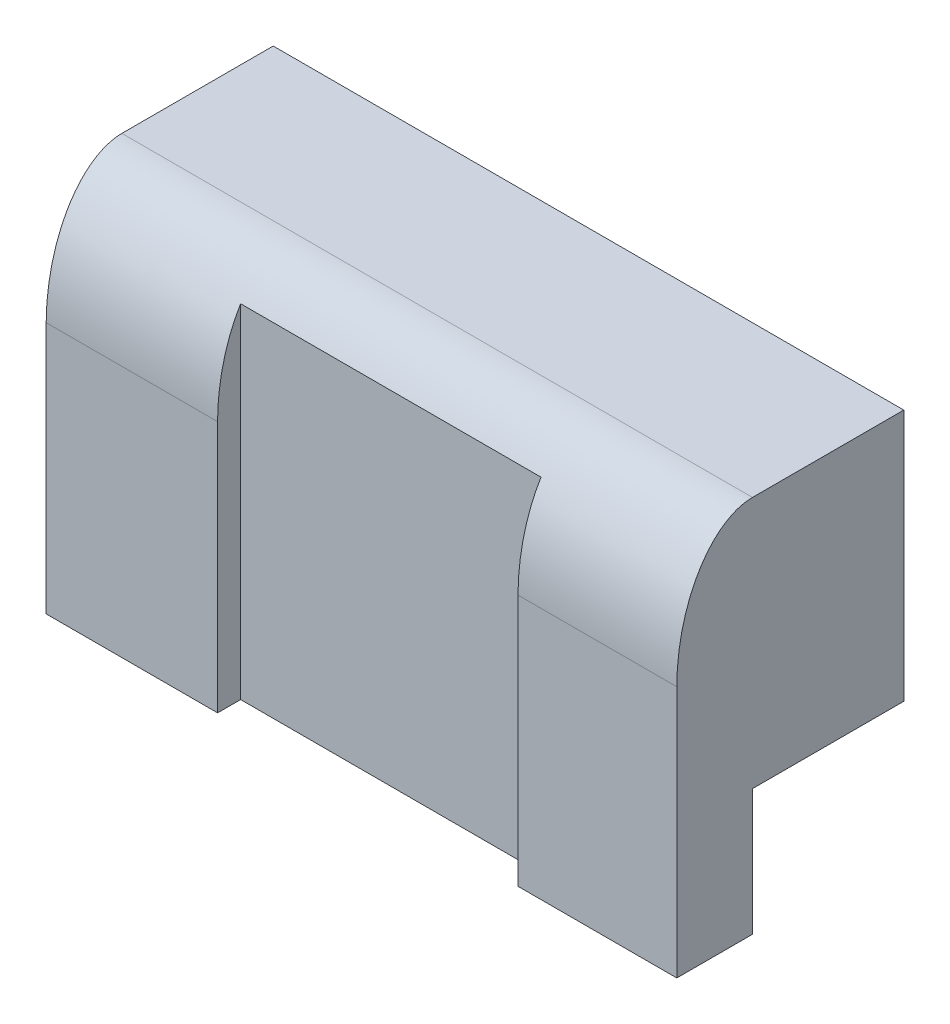
SolidWorks part; units mm, degrees
ref_plane "Front Plane" through (0, 0, 0) normal (0, 0, 1) x (1, 0, 0)
ref_plane "Top Plane" through (0, 0, 0) normal (0, 1, 0) x (1, 0, 0)
ref_plane "Right Plane" through (0, 0, 0) normal (1, 0, 0) x (0, 0, -1)
sketch "Sketch1" plane through (0, 0, 0) normal (1, 0, 0) x (0, 0, -1)
  line L1 (0, 0) -> (3, 0)
  line L2 (0, 0) -> (0, 15)
  line L3 (0, 15) -> (3, 15)
  line L4 (3, 0) -> (3, 15)
  dimension "D1" = 3
  dimension "D2" = 15
extrude "Boss-Extrude1" add sketch "Sketch1" along normal blind 25
sketch "Sketch2" plane through (0, 0, -3) normal (0, 0, -1) x (-1, 0, 0)
  line L0 (-25, 0) -> (-25, 15) construction
  line L1 (0, 15) -> (-25, 15)
  line L2 (0, 15) -> (0, 5)
  line L3 (0, 5) -> (-25, 5)
  line L4 (-25, 15) -> (-25, 5)
  dimension "D1" = 10
extrude "Boss-Extrude2" add sketch "Sketch2" along normal blind 6
fillet "Fillet1" radius 5 1 edges at (12.5, 15, 0) second distance 3 first distance on face at (12.5, 7.5, 0)
hole_wizard "Ø3.0mm Dowel Hole1" positions "Sketch3" profile "Sketch4" hole size "Ø3.0" standard "ANSI Metric"
sketch "Sketch3" plane through (0, 5, 0) normal (0, -1, 0) x (-1, 0, 0)
  line L0 (0, 9) -> (0, 3) construction
  line L1 (-25, 3) -> (0, 3) construction
  line L2 (-25, 9) -> (-25, 3) construction
  point P0 (-3, 6)
  point P11 (-18, 6)
  point P20 (-7, 6)
  point P22 (-22, 6)
  dimension "D1" = 3
  dimension "D2" = 3
  dimension "D3" = 15
  dimension "D4" = 3
  dimension "D5" = 3
  dimension "D6" = 15
sketch "Sketch4" plane through (3, 5, -6) normal (1, 0, 0) x (0, 0, -1)
  line L0 (0, 0) -> (0, 5.9013)
  line L1 (0, 5.9013) -> (1.5, 5)
  line L2 (1.5, 5) -> (1.5, 0)
  line L5 (1.5, 0) -> (0, 0)
  line L10 (0, 5.9013) -> (-1.5, 5) construction
  line L11 (0, -6.35) -> (0, 107.95) construction
  dimension "Hole Dia." = 3
  dimension "Hole Depth" = 5
  dimension "Drill Angle" = 118
sketch "Sketch5" plane through (0, 15, 0) normal (0, 1, 0) x (1, 0, 0)
  line L1 (6.7949, -1.1173) -> (18.7048, -1.1173)
  line L2 (6.7949, -1.1173) -> (6.7949, 0.913)
  line L3 (6.7949, 0.913) -> (18.7048, 0.913)
  line L4 (18.7048, -1.1173) -> (18.7048, 0.913)
extrude "Cut-Extrude1" cut sketch "Sketch5" against normal blind 18
